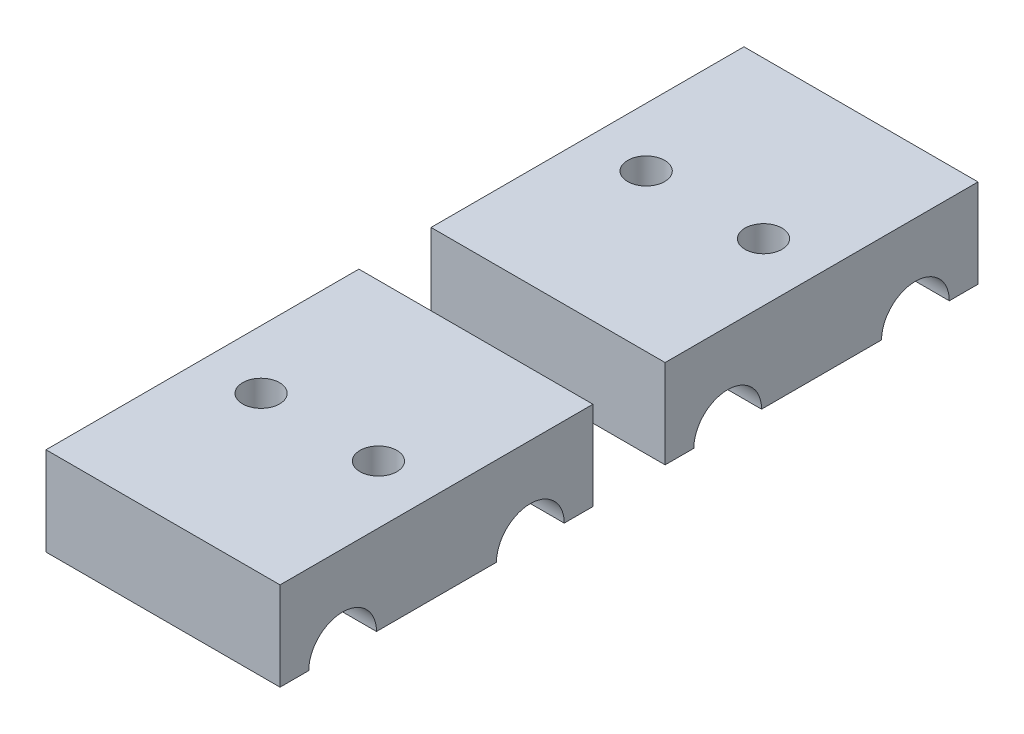
SolidWorks part; units mm, degrees
note: The reader was unsure of these and kept them because the rebuilt part matched: shared geometry of "Sketch9<3>", "Sketch9<4>".
ref_plane "Front Plane" through (0, 0, 0) normal (0, 0, 1) x (1, 0, 0)
ref_plane "Top Plane" through (0, 0, 0) normal (0, 1, 0) x (1, 0, 0)
ref_plane "Right Plane" through (0, 0, 0) normal (1, 0, 0) x (0, 0, -1)
sketch "Sketch6" plane through (0, 0, 0) normal (0, 1, 0) x (1, 0, 0)
  line L0 (0, 0) -> (0, 5)
  line L1 (0, 5) -> (19, 5)
  line L2 (19, 5) -> (19, 2.75)
  line L6 (19, 2.75) -> (16, 2.75)
  line L7 (16, 2.75) -> (15, 2.25)
  line L8 (15, 2.25) -> (15, 2.75)
  line L9 (15, 2.75) -> (9, 2.75)
  line L10 (9, 2.75) -> (8, 2.25)
  line L11 (8, 2.25) -> (8, 2.75)
  line L12 (8, 2.75) -> (0, 2.75)
  line L18 (0, 0) -> (15, 0)
  dimension "D1" = 0.5
  dimension "D2" = 19
  dimension "D3" = 3
  dimension "D4" = 5
  dimension "D5" = 2.25
  dimension "D6" = 2.25
  dimension "D7" = 2.25
  dimension "D10" = 1
  dimension "D11" = 1
  dimension "D12" = 6
  dimension "D13" = 8
  dimension "D20" = 15
revolve "Revolve1" add sketch "Sketch6" angle 180 about L18
sketch "Sketch9" plane through (0, 0, 0) normal (0, 0, 1) x (1, 0, 0)
  line L0 (0, 0) -> (0, 3.25)
  line L1 (0, 3.25) -> (0, 5)
  line L2 (0, 5) -> (19, 5)
  line L3 (19, 5) -> (19, 2.75)
  line L4 (19, 2.75) -> (19, 0)
  line L5 (19, 0) -> (0, 0)
  line L6 (0, 3.25) -> (19, 2.75)
  dimension "D1" = 3.25
extrude "Boss-Extrude1" add sketch "Sketch9" along normal blind 9.25 and the other way blind 9.25 contours L1 L6 L3 L2
extrude "Boss-Extrude2" add sketch "Sketch9<3>" along normal blind 5.75 from offset 3.5 contours L6 L0 L5 L4
sketch "Sketch9<3>" plane through (0, 0, 0) normal (0, 0, 1) x (1, 0, 0) same geometry as "Sketch9"
extrude "Boss-Extrude3" add sketch "Sketch9<4>" against normal blind 5.75 from offset 3.5 contours L6 L0 L5 L4 offset against normal yes
sketch "Sketch9<4>" plane through (0, 0, 0) normal (0, 0, 1) x (1, 0, 0) same geometry as "Sketch9"
sketch "Sketch13" plane through (0, 0, 0) normal (-1, 0, 0) x (0, 0, 1)
  line L0 (-2.75, 0) -> (-9.25, 0) construction
  line L1 (-2.75, 0) -> (2.75, 0)
  line L2 (-2.75, 0) -> (-2.75, 2.75)
  line L3 (-2.75, 2.75) -> (2.75, 2.75)
  line L4 (2.75, 0) -> (2.75, 2.75)
  point P6 (0, 0)
  dimension "D1" = 5.5
  dimension "D2" = 2.75
extrude "Cut-Extrude9" cut sketch "Sketch13" against normal blind 1.75
ref_plane "Plane3" through (0, 0, -7.62) normal (0, 0, 1) x (1, 0, 0)
mirror "Mirror4" about plane through (0, 0, -7.62) normal (0, 0, 1) of bodies 146
sketch "Sketch16" plane through (0, 5, 0) normal (0, 1, 0) x (1, 0, 0)
  line L0 (0, 24.49) -> (0, -9.25) construction
  line L1 (0, 20.32) -> (19, 20.32)
  line L2 (0, 20.32) -> (0, -5.08)
  line L3 (0, -5.08) -> (19, -5.08)
  line L4 (19, 20.32) -> (19, -5.08)
  line L5 (19, 24.49) -> (19, -9.25) construction
  dimension "D1" = 2.33
  dimension "D2" = 2.33
extrude "Cut-Extrude10" cut sketch "Sketch16" against normal through all
sketch "Sketch17" plane through (0, 5, 0) normal (0, 1, 0) x (1, 0, 0)
  line L1 (0, -5.08) -> (19, -5.08)
  line L2 (0, -5.08) -> (0, 20.32)
  line L3 (0, 20.32) -> (19, 20.32)
  line L4 (19, -5.08) -> (19, 20.32)
extrude "Boss-Extrude4" add sketch "Sketch17" along normal blind 2.195
sketch "Sketch18" plane through (0, 7.195, 0) normal (0, 1, 0) x (1, 0, 0)
  line L0 (0, 20.32) -> (0, -5.08) construction
  line L1 (0, -5.08) -> (19, -5.08) construction
  circle A0 centre (4.7625, 7.62) radius 1.5
  circle A1 centre (14.2875, 7.62) radius 1.5
  point P6 (9.5, -5.08)
  point P9 (0, 0)
  point P10 (0, 0)
  point P11 (0, 0)
  point P13 (11.4232, -5.08)
  dimension "D1" = 3
  dimension "D4" = 3
  dimension "D2" = 4.7625
  dimension "D3" = 12.7
  dimension "D5" = 12.7
  dimension "D6" = 9.525
extrude "Cut-Extrude11" cut sketch "Sketch18" against normal through all contours A1 | A0
ref_plane "Plane5" through (0, 0, -23.25) normal (0, 0, -1) x (-1, 0, 0)
mirror "Mirror1" about plane through (0, 0, -23.25) normal (0, 0, -1) of bodies 153 122 138 137 141
